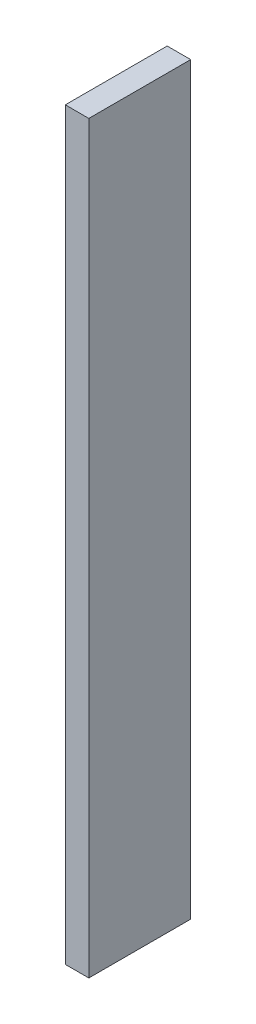
SolidWorks part; units mm, degrees
material "6061-T6 (SS)"
ref_plane "Front" through (0, 0, 0) normal (0, 0, 1) x (1, 0, 0)
ref_plane "Top" through (0, 0, 0) normal (0, 1, 0) x (1, 0, 0)
ref_plane "Right" through (0, 0, 0) normal (1, 0, 0) x (0, 0, -1)
sketch "Sketch1" plane through (0, 0, 0) normal (0, 1, 0) x (1, 0, 0)
  line L1 (-76.2, 330.2) -> (76.2, 330.2)
  line L2 (-76.2, 330.2) -> (-76.2, -330.2)
  line L3 (-76.2, -330.2) -> (76.2, -330.2)
  line L4 (76.2, 330.2) -> (76.2, -330.2)
  line L5 (-76.2, 330.2) -> (76.2, -330.2) construction
  line L6 (-76.2, -330.2) -> (76.2, 330.2) construction
  point P0 (0, 0)
  dimension "D1" = 152.4
  dimension "D2" = 660.4
extrude "Boss-Extrude1" add sketch "Sketch1" along normal blind 4826
